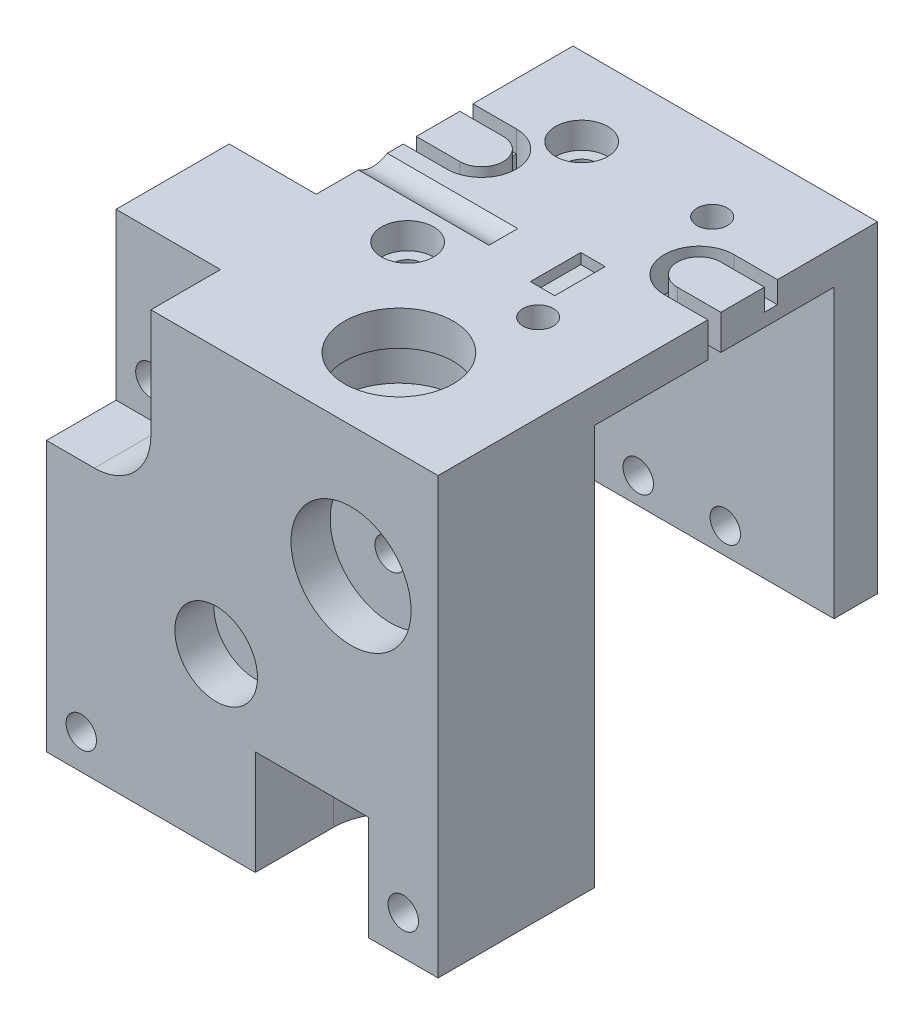
SolidWorks part; units mm, degrees
material "ABS"
ref_plane "Front Plane" through (0, 0, 0) normal (0, 0, 1) x (1, 0, 0)
ref_plane "Top Plane" through (0, 0, 0) normal (0, 1, 0) x (1, 0, 0)
ref_plane "Right Plane" through (0, 0, 0) normal (1, 0, 0) x (0, 0, -1)
sketch "Sketch1" plane through (0, 0, 0) normal (0, 1, 0) x (1, 0, 0)
  line L1 (-17.5, -14) -> (17.5, -14)
  line L2 (-17.5, -14) -> (-17.5, 14)
  line L3 (-17.5, 14) -> (17.5, 14)
  line L4 (17.5, -14) -> (17.5, 14)
  line L5 (-17.5, -14) -> (17.5, 14) construction
  line L6 (-17.5, 14) -> (17.5, -14) construction
  point P0 (0, 0)
  dimension "D1" = 28
  dimension "D2" = 35
extrude "Boss-Extrude1" add sketch "Sketch1" along normal blind 4
sketch "Sketch2" plane through (0, 4, 0) normal (0, 1, 0) x (1, 0, 0)
  line L0 (-17.5, -14) -> (17.5, -14) construction
  line L1 (-17.5, 14) -> (-17.5, -14) construction
  line L2 (-17.5, -14) -> (17.5, -14) construction
  line L3 (17.5, 14) -> (-17.5, 14) construction
  circle A0 centre (-7.5, -10) radius 1.75
  circle A1 centre (-7.5, 10) radius 1.75
  circle A2 centre (7.5, -10) radius 1.75
  circle A3 centre (7.5, 10) radius 1.75
  dimension "D1" = 3.5
  dimension "D2" = 3.5
  dimension "D5" = 3.5
  dimension "D8" = 3.5
  dimension "D3" = 20
  dimension "D4" = 4
  dimension "D6" = 15
  dimension "D7" = 10
  dimension "D9" = 15
  dimension "D10" = 4
  dimension "D11" = 4
extrude "Cut-Extrude1" cut sketch "Sketch2" against normal through all
sketch "Sketch3" plane through (0, 0, 14) normal (0, 0, 1) x (1, 0, 0)
  line L0 (17.5, 4) -> (17.5, 0) construction
  line L1 (-17.5, 4) -> (17.5, 4)
  line L2 (-17.5, 4) -> (-17.5, -46)
  line L3 (-17.5, -46) -> (17.5, -46)
  line L4 (17.5, 4) -> (17.5, -46)
  dimension "D1" = 50
extrude "Boss-Extrude2" add sketch "Sketch3" along normal blind 17.5 and the other way blind 0.5
sketch "Sketch7" plane through (0, 0, -14) normal (0, 0, -1) x (-1, 0, 0)
  line L1 (-17.5, 4) -> (17.5, 4)
  line L2 (-17.5, 4) -> (-17.5, -33)
  line L3 (-17.5, -33) -> (17.5, -33)
  line L4 (17.5, 4) -> (17.5, -33)
  line L6 (17.5, 4) -> (17.5, 0) construction
  dimension "D1" = 37
extrude "Boss-Extrude3" add sketch "Sketch7" along normal blind 5
sketch "Sketch10" plane through (0, 0, -19) normal (0, 0, -1) x (-1, 0, 0)
  line L1 (0, 4) -> (0, -33) construction
  line L3 (17.5, 4) -> (-17.5, 4) construction
  line L4 (-17.5, -33) -> (17.5, -33) construction
  circle A1 centre (-5, -30) radius 1.75
  circle A2 centre (5, -30) radius 1.75
  dimension "D1" = 3
  dimension "D2" = 3.5
  dimension "D4" = 3.5
  dimension "D3" = 5
  dimension "D5" = 5
extrude "Cut-Extrude6" cut sketch "Sketch10" against normal blind 5
sketch "Sketch18" plane through (0, 4, 0) normal (0, 1, 0) x (1, 0, 0)
  line L0 (-17.5, -10) -> (-10.5, -10)
  line L1 (-17.5, 19) -> (-17.5, -31.5) construction
  line L2 (-10.5, -10) -> (-10.5, -11.5)
  line L3 (-10.5, -11.5) -> (-17.5, -11.5)
  line L4 (-17.5, -11.5) -> (-17.5, -10)
  line L5 (17.5, 10) -> (10.5, 10)
  line L6 (17.5, -31.5) -> (17.5, 19) construction
  line L7 (10.5, 10) -> (10.5, 11.5)
  line L8 (10.5, 11.5) -> (17.5, 11.5)
  line L9 (17.5, 11.5) -> (17.5, 10)
  circle A0 centre (-7.5, -10) radius 1.75 construction
  circle A1 centre (7.5, 10) radius 1.75 construction
  dimension "D4" = 3
  dimension "D1" = 0
  dimension "D2" = 3
  dimension "D3" = 1.5
  dimension "D5" = 0
  dimension "D6" = 1.5
extrude "Cut-Extrude14" [suppressed] cut sketch "Sketch18" against normal through all
sketch "Sketch19" plane through (0, 4, 0) normal (0, 1, 0) x (1, 0, 0)
  line L0 (-17.5, 19) -> (-17.5, -31.5) construction
  line L1 (17.5, -31.5) -> (17.5, 19) construction
  circle A0 centre (-7.5, 0) radius 1.75
  circle A1 centre (7.5, 0) radius 1.75
  dimension "D3" = 3.5
  dimension "D4" = 3.5
  dimension "D1" = 10
  dimension "D2" = 10
extrude "Cut-Extrude15" [suppressed] cut sketch "Sketch19" against normal through all
sketch "Sketch20" [suppressed] plane through (0, 0, 0) normal (0, -1, 0) x (1, 0, 0)
  line L1 (10.9641, 0) -> (9.2321, 3)
  line L2 (9.2321, 3) -> (5.7679, 3)
  line L3 (5.7679, 3) -> (4.0359, 0)
  line L4 (4.0359, 0) -> (5.7679, -3)
  line L5 (5.7679, -3) -> (9.2321, -3)
  line L6 (9.2321, -3) -> (10.9641, 0)
  line L7 (-10.9641, 0) -> (-9.2321, -3)
  line L8 (-9.2321, -3) -> (-5.7679, -3)
  line L9 (-5.7679, -3) -> (-4.0359, 0)
  line L10 (-4.0359, 0) -> (-5.7679, 3)
  line L11 (-5.7679, 3) -> (-9.2321, 3)
  line L12 (-9.2321, 3) -> (-10.9641, 0)
  circle A0 centre (7.5, 0) radius 3 construction
  circle A1 centre (-7.5, 0) radius 3 construction
  dimension "D1" = 6
  dimension "D2" = 6
extrude "Cut-Extrude16" [suppressed] cut sketch "Sketch20" against normal blind 3
sketch "Sketch21" [suppressed] plane through (0, 4, 0) normal (0, 1, 0) x (1, 0, 0)
  line L0 (-10.5, -10) -> (-17.5, -10) construction
  circle A0 centre (-17, -10) radius 0.5
  dimension "D1" = 1
extrude "Cut-Extrude17" [suppressed] cut sketch "Sketch21" against normal blind 4
pattern_linear "LPattern2" [suppressed] count 4 spacing 2 of bodies 121
fillet "Fillet2" [suppressed] radius 0.15
sketch "Sketch24" plane through (-17.5, 0, 0) normal (-1, 0, 0) x (0, 0, 1)
  line L5 (31.5, -46) -> (13.5, -46) construction
  line L6 (13.5, -46) -> (31.5, -46)
  line L7 (13.5, -46) -> (13.5, 0)
  line L8 (13.5, 0) -> (31.5, 0)
  line L9 (31.5, -46) -> (31.5, 0)
  line L10 (13.5, 0) -> (13.5, -46) construction
  line L11 (31.5, 4) -> (31.5, -46) construction
extrude "Boss-Extrude4" add sketch "Sketch24" along normal blind 10
sketch "Sketch37" plane through (-17.5, 0, 0) normal (-1, 0, 0) x (0, 0, 1)
  line L1 (10.5, 4) -> (23.5, 4)
  line L2 (10.5, 4) -> (10.5, -10)
  line L3 (10.5, -10) -> (23.5, -10)
  line L4 (23.5, 4) -> (23.5, -10)
  dimension "D1" = 3
  dimension "D2" = 10
  dimension "D3" = 14
extrude "Boss-Extrude9" add sketch "Sketch37" along normal blind 10
sketch "Sketch22" plane through (0, 0, 31.5) normal (0, 0, 1) x (1, 0, 0)
  line L0 (-27.5, -46) -> (-27.5, 0) construction
  line L1 (-15.5, 0) -> (-27.5, 0)
  line L2 (-27.5, -46) -> (17.5, -46) construction
  line L4 (-27.5, 0) -> (-17.5, 0) construction
  line L5 (-27.5, -46) -> (17.5, -46) construction
  line L6 (-27.5, 0) -> (-27.5, -15)
  line L9 (-27.5, -15) -> (-22, -15)
  line L10 (-15.5, 0) -> (-15.5, -8.5)
  line L11 (9.5, -46) -> (-3.5, -46)
  line L12 (9.5, -46) -> (9.5, -34)
  line L13 (9.5, -34) -> (-3.5, -34)
  line L14 (-3.5, -46) -> (-3.5, -34)
  line L16 (-15.5, 0) -> (-17.5, 0)
  line L17 (-15.5, 0) -> (-15.5, 4)
  line L18 (-15.5, 4) -> (-17.5, 4)
  line L19 (-17.5, 0) -> (-17.5, 4)
  circle A0 centre (-23.5, -42) radius 1.75
  circle A1 centre (13.5, -41.5) radius 1.75
  circle A3 centre (7.5, -11) radius 6.9
  circle A4 centre (-8, -26.5) radius 4.75
  arc A5 (-22, -15) -> (-15.5, -8.5) centre (-22, -8.5) ccw
  circle A6 centre (7.5, -11) radius 1.75
  circle A7 centre (-23.5, -11) radius 1.75
  point P21 (-15.5, -15)
  line M3 (-17.5, 4) -> (-17.5, 0)
  line M6 (17.5, 4) -> (-17.5, 4)
  line M24 (-17.5, 0) -> (-27.5, 0)
  line M25 (-27.5, 0) -> (-27.5, -46)
  dimension "D3" = 3.5
  dimension "D6" = 35
  dimension "D7" = 3.5
  dimension "D9" = 13.8
  dimension "D11" = 9.5
  dimension "D15" = 6.5
  dimension "D22" = 3.5
  dimension "D23" = 3.5
  dimension "D2" = 4
  dimension "D4" = 4.5
  dimension "D5" = 4
  dimension "D8" = 12
  dimension "D10" = 35
  dimension "D12" = 19.5
  dimension "D13" = 19.5
  dimension "D14" = 31
  dimension "D16" = 24
  dimension "D17" = 13
  dimension "D18" = 12
  dimension "D19" = 41
  dimension "D20" = 4
  dimension "D21" = 35
extrude "Cut-Extrude19" cut sketch "Sketch22" against normal up to next contours A0 | A1 | A7 | A6 region at (-23.5, -42, 31.5) region at (13.5, -41.5, 31.5) region at (7.5, -11, 31.5) region at (-23.5, -11, 31.5)
extrude "Cut-Extrude20" cut sketch "Sketch22<3>" against normal blind 4.5 contours A3 | A4
sketch "Sketch22<3>" plane through (0, 0, 31.5) normal (0, 0, 1) x (1, 0, 0) same geometry as "Sketch22"
extrude "Cut-Extrude24" cut sketch "Sketch22<5>" against normal blind 8 contours L9 A5 L10 L1 A7 M24 M25 | L1 L17 M6 M3 region at (-21.6364, -6.9513, 31.5) region at (-16.5, 2, 31.5)
sketch "Sketch22<5>" plane through (0, 0, 31.5) normal (0, 0, 1) x (1, 0, 0) same geometry as "Sketch22"
extrude "Cut-Extrude21" cut sketch "Sketch22<4>" against normal blind 15.5 contours L14 L13 L12 L11
sketch "Sketch22<4>" plane through (0, 0, 31.5) normal (0, 0, 1) x (1, 0, 0) same geometry as "Sketch22"
fillet "Fillet3" radius 6.5 2 edges at (9.5, -40, 16) (-3.5, -40, 16)
sketch "Sketch26" plane through (0, -34, 0) normal (0, -1, 0) x (1, 0, 0)
  line L0 (9.5, 31.5) -> (-3.5, 31.5) construction
  line L1 (-3.5, 22.5) -> (-3.5, 31.5) construction
  circle A0 centre (3, 21.5) radius 2.25
  dimension "D1" = 4.5
  dimension "D2" = 10
  dimension "D3" = 6.5
extrude "Cut-Extrude22" cut sketch "Sketch26" against normal through all
sketch "Sketch27" plane through (0, 4, 0) normal (0, 1, 0) x (1, 0, 0)
  circle A0 centre (3, -21.5) radius 6.25
  dimension "D1" = 12.5
extrude "Cut-Extrude23" cut sketch "Sketch27" against normal blind 8
sketch "Sketch29" plane through (0, 0, 13.5) normal (0, 0, -1) x (-1, 0, 0)
  line L1 (-4.1514, -11) -> (-5.8257, -8.1)
  line L2 (-5.8257, -8.1) -> (-9.1743, -8.1)
  line L3 (-9.1743, -8.1) -> (-10.8486, -11)
  line L4 (-10.8486, -11) -> (-9.1743, -13.9)
  line L5 (-9.1743, -13.9) -> (-5.8257, -13.9)
  line L6 (-5.8257, -13.9) -> (-4.1514, -11)
  line L7 (20.1514, -11) -> (21.8257, -13.9)
  line L8 (21.8257, -13.9) -> (25.1743, -13.9)
  line L9 (25.1743, -13.9) -> (26.8486, -11)
  line L10 (26.8486, -11) -> (25.1743, -8.1)
  line L11 (25.1743, -8.1) -> (21.8257, -8.1)
  line L12 (21.8257, -8.1) -> (20.1514, -11)
  line L13 (-10.1514, -41.5) -> (-11.8257, -38.6)
  line L14 (-11.8257, -38.6) -> (-15.1743, -38.6)
  line L15 (-15.1743, -38.6) -> (-16.8486, -41.5)
  line L16 (-16.8486, -41.5) -> (-15.1743, -44.4)
  line L17 (-15.1743, -44.4) -> (-11.8257, -44.4)
  line L18 (-11.8257, -44.4) -> (-10.1514, -41.5)
  line L25 (23.5, -45.3486) -> (26.4, -43.6743)
  line L26 (26.4, -43.6743) -> (26.4, -40.3257)
  line L27 (26.4, -40.3257) -> (23.5, -38.6514)
  line L28 (23.5, -38.6514) -> (20.6, -40.3257)
  line L29 (20.6, -40.3257) -> (20.6, -43.6743)
  line L30 (20.6, -43.6743) -> (23.5, -45.3486)
  circle A0 centre (-7.5, -11) radius 2.9 construction
  circle A1 centre (23.5, -11) radius 2.9 construction
  circle A2 centre (-13.5, -41.5) radius 2.9 construction
  circle A3 centre (23.5, -42) radius 2.9 construction
  dimension "D1" = 5.8
  dimension "D2" = 5.8
  dimension "D3" = 5.8
  dimension "D4" = 5.8
extrude "Cut-Extrude25" cut sketch "Sketch29" against normal blind 3 and the other way blind 3
sketch "Sketch30" plane through (0, 4, 0) normal (0, 1, 0) x (1, 0, 0)
  circle A0 centre (-7.5, 10) radius 3
  circle A1 centre (-7.5, -10) radius 3
  dimension "D1" = 6
  dimension "D2" = 6
extrude "Cut-Extrude26" cut sketch "Sketch30" against normal blind 3
sketch "Sketch31" plane through (0, 4, 0) normal (0, 1, 0) x (1, 0, 0)
  line L0 (-17.5, 0) -> (17.5, 0) construction
  line L1 (-17.5, 19) -> (-17.5, -10.5) construction
  line L2 (17.5, -31.5) -> (17.5, 19) construction
  line L4 (-17.5, 1) -> (-12.5, 1)
  line L10 (-17.5, -0.5) -> (-12.5, -0.5)
  line L11 (-17.5, 1) -> (-17.5, -0.5)
  line L12 (-12.5, 6) -> (-12.5, 7.5)
  arc A0 (-12.5, 1) -> (-12.5, 6) centre (-12.5, 3.5) ccw
  arc A2 (-12.5, -0.5) -> (-12.5, 7.5) centre (-12.5, 3.5) ccw
  dimension "D4" = 2.5
  dimension "D1" = 1
  dimension "D2" = 1.5
  dimension "D3" = 5
extrude "Cut-Extrude27" cut sketch "Sketch31" against normal through all
sketch "Sketch32" plane through (0, 4, 0) normal (0, 1, 0) x (1, 0, 0)
  line L0 (-17.5, 19) -> (-17.5, 1) construction
  line L1 (-12.5, 7.5) -> (-17.5, 7.5)
  line L2 (-12.5, 7.5) -> (-12.5, 6)
  line L3 (-12.5, 6) -> (-17.5, 6)
  line L4 (-17.5, 7.5) -> (-17.5, 6)
  arc A0 (-12.5, -0.5) -> (-12.5, 7.5) centre (-12.5, 3.5) ccw construction
extrude "Cut-Extrude28" cut sketch "Sketch32" against normal blind 2.5
sketch "Sketch33" plane through (-17.5, 0, 0) normal (-1, 0, 0) x (0, 0, 1)
  line L0 (0.5, 0) -> (0.5, 4) construction
  line L1 (0.5, 4) -> (10.5, 4) construction
  circle A0 centre (4, 6.5) radius 3
  dimension "D3" = 6
  dimension "D1" = 3.5
  dimension "D2" = 2.5
extrude "Cut-Extrude29" cut sketch "Sketch33" against normal blind 15
sketch "Sketch34" plane through (0, 4, 0) normal (0, 1, 0) x (1, 0, 0)
  line L1 (3.5, -6.9) -> (6.3, -6.9)
  line L2 (3.5, -6.9) -> (3.5, -1.1)
  line L3 (3.5, -1.1) -> (6.3, -1.1)
  line L4 (6.3, -6.9) -> (6.3, -1.1)
  circle A0 centre (7.5, -10) radius 1.75 construction
  dimension "D1" = 2.8
  dimension "D2" = 5.8
  dimension "D3" = 3.1
  dimension "D4" = 1.2
extrude "Cut-Extrude30" cut sketch "Sketch34" against normal blind 1.2
ref_plane "Plane1" through (0, 0, 0) normal (-1, 0, 0) x (0, 0, 1)
mirror "Mirror1" about plane through (0, 0, 0) normal (-1, 0, 0) of "Cut-Extrude28", "Cut-Extrude27"
sketch "Sketch38" plane through (0, -4, 0) normal (0, 1, 0) x (1, 0, 0)
  circle A0 centre (3, -21.5) radius 7
  dimension "D1" = 14
extrude "Cut-Extrude31" cut sketch "Sketch38" along normal blind 4
sketch "Sketch39" plane through (-27.5, 0, 0) normal (-1, 0, 0) x (0, 0, 1)
  line L0 (13.5, -46) -> (17, -46)
  line L1 (13.5, -46) -> (31.5, -46) construction
  line L2 (13.5, -46) -> (13.5, -19)
  line L3 (13.5, -10) -> (13.5, -46) construction
  line L4 (13.5, -19) -> (17, -19)
  line L5 (20.5, -22.5) -> (20.5, -26)
  line L6 (20.5, -26) -> (27.5, -26)
  line L7 (27.5, -26) -> (27.5, -39)
  line L8 (27.5, -39) -> (20.5, -39)
  line L9 (20.5, -39) -> (20.5, -42.5)
  line L11 (27.5, -29) -> (23.5, -29)
  line L12 (27.5, -29) -> (27.5, -36)
  line L13 (27.5, -36) -> (23.5, -36)
  line L14 (23.5, -29) -> (23.5, -36)
  line L15 (13.5, -26) -> (18.5, -26)
  line L16 (13.5, -26) -> (13.5, -39)
  line L17 (13.5, -39) -> (18.5, -39)
  line L18 (18.5, -26) -> (18.5, -39)
  arc A0 (17, -46) -> (20.5, -42.5) centre (17, -42.5) ccw
  arc A1 (17, -19) -> (20.5, -22.5) centre (17, -22.5) cw
  point P15 (20.5, -46)
  point P18 (20.5, -19)
  dimension "D7" = 3.5
  dimension "D1" = 7
  dimension "D2" = 27
  dimension "D3" = 7
  dimension "D4" = 7
  dimension "D5" = 7
  dimension "D6" = 13
  dimension "D8" = 4
  dimension "D9" = 7
  dimension "D10" = 3
  dimension "D11" = 5
extrude "Cut-Extrude32" cut sketch "Sketch39" against normal blind 3 contours L18 L15 L2 L17 | L11 L14 L13 L7 region at (-27.5, -32.5, 16) region at (-27.5, -32.5, 25.5)
sketch "Sketch40" plane through (-27.5, 0, 0) normal (-1, 0, 0) x (0, 0, 1)
  line L0 (13.5, -10) -> (13.5, -26) construction
  line L1 (13.5, -46) -> (31.5, -46) construction
  circle A0 centre (17, -22.5) radius 1.4
  dimension "D3" = 2.8
  dimension "D1" = 3.5
  dimension "D2" = 23.5
extrude "Cut-Extrude33" cut sketch "Sketch40" against normal blind 15
sketch "Sketch41" plane through (-27.5, 0, 0) normal (-1, 0, 0) x (0, 0, 1)
  line L0 (13.5, -39) -> (13.5, -46) construction
  line L1 (13.5, -46) -> (31.5, -46) construction
  line L2 (20.5, -42.5) -> (20.5, -39)
  line L15 (23, -42.5) -> (23, -39)
  line L16 (17, -46) -> (17, -48.5)
  line L17 (20.5, -39) -> (23, -39)
  line L18 (17, -46) -> (21.8734, -46)
  circle A0 centre (17, -42.5) radius 1.25
  arc A1 (17, -46) -> (20.5, -42.5) centre (17, -42.5) ccw
  arc A2 (17, -48.5) -> (23, -42.5) centre (17, -42.5) ccw
  line M16 (13.5, -46) -> (31.5, -46)
  dimension "D5" = 2.5
  dimension "D1" = 3.5
  dimension "D2" = 3.5
  dimension "D3" = 3.5
  dimension "D4" = 2.5
extrude "Boss-Extrude10" add sketch "Sketch41" along normal blind 2.5 contours A0 | A2 L15 L17 L2 A1 M16 region at (-27.5, -42.7022, 21.4056) region at (-27.5, -42.5, 17)
